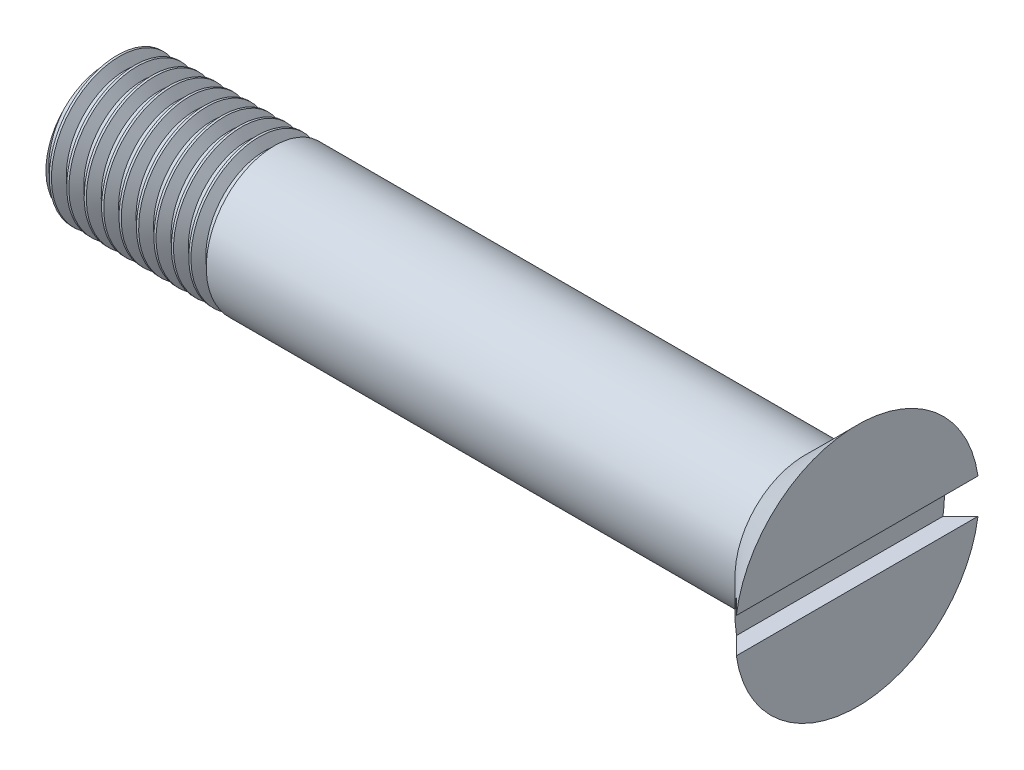
SolidWorks part; units mm, degrees
ref_plane "Front Plane" through (0, 0, 0) normal (0, 0, 1) x (1, 0, 0)
ref_plane "Top Plane" through (0, 0, 0) normal (0, 1, 0) x (1, 0, 0)
ref_plane "Right Plane" through (0, 0, 0) normal (1, 0, 0) x (0, 0, -1)
sketch "Sketch1" plane through (0, 0, 0) normal (0, 1, 0) x (1, 0, 0)
  line L0 (0, 0) -> (0, 11662.0861) construction
  line L1 (0, 0) -> (11662.0861, 0) construction
  line L2 (-45, 0) -> (-42.6906, -4)
  line L3 (-42.6906, -4) -> (-3, -4)
  line L4 (-3, -4) -> (0, -7)
  line L5 (0, -7) -> (0, 0)
  line L6 (0, 0) -> (-45, 0)
  dimension "D1" = 45
  dimension "D2" = 45
  dimension "D3" = 3
  dimension "D4" = 8
  dimension "D5" = 60
revolve "Revolve1" add sketch "Sketch1" angle 360 about L6
sketch "Sketch2" plane through (0, 0, 0) normal (1, 0, 0) x (0, 0, -1)
  line L1 (-8.119, 1) -> (8.119, 1)
  line L2 (-8.119, 1) -> (-8.119, -1)
  line L3 (-8.119, -1) -> (8.119, -1)
  line L4 (8.119, 1) -> (8.119, -1)
  line L5 (-8.119, 1) -> (8.119, -1) construction
  line L6 (-8.119, -1) -> (8.119, 1) construction
  point P1 (0, 0)
  dimension "D1" = 2
extrude "Cut-Extrude1" cut sketch "Sketch2" against normal blind 1
thread "Thread1" pitch 1 method cut profile "Thread Profile1" start angle 0, offset 1, length 10, pitch 1, diameter 8
ref_plane "Plane1" through (-43.6906, 0, -4) normal (0, -1, 0) x (0, 0, -1)
sketch "Thread Profile1" plane through (-43.6906, 0, -4) normal (0, -1, 0) x (0, 0, -1)
  line L0 (0, 0) -> (0, 1) construction
  line L11 (0, 0) -> (0, 0.875)
  line L12 (0, 0.875) -> (-0.5413, 0.5625)
  line L13 (-0.5413, 0.5625) -> (-0.5413, 0.3125)
  line L15 (-0.5413, 0.3125) -> (0, 0)
  line L17 (-0.5413, 0.4375) -> (0, 0.4375) construction
  point P2 (0, 0)
  dimension "Pitch" = 1
  dimension "Profile_Angle" = 60
  dimension "Profile_Land" = 0.25
  dimension "Profile_Height" = 0.5413
